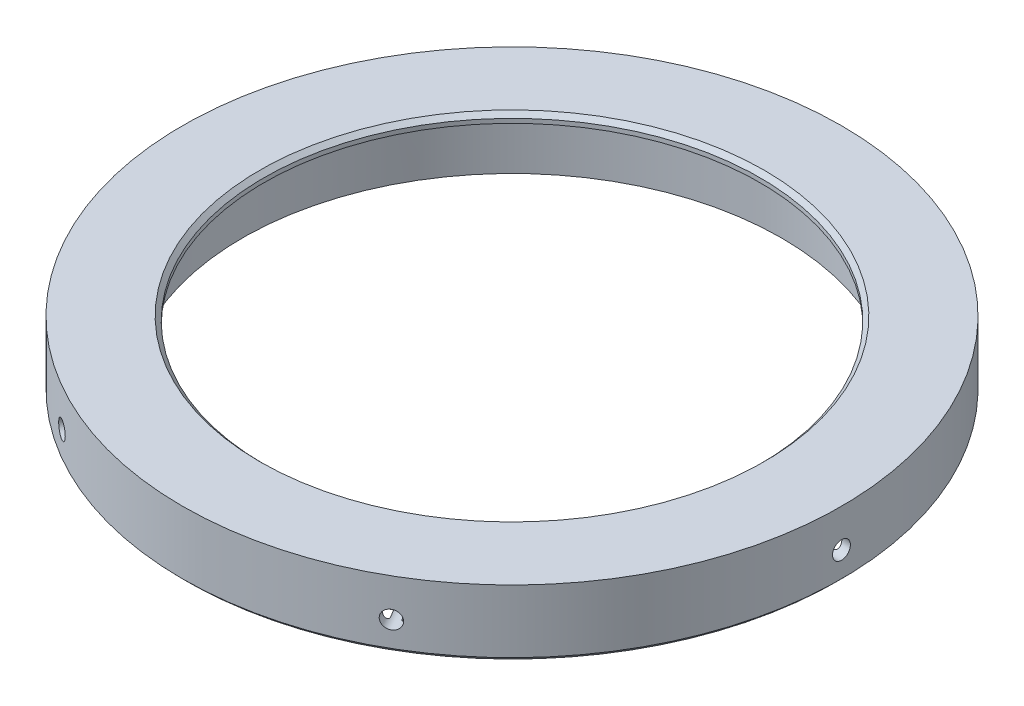
SolidWorks part; units mm, degrees
ref_plane "Front" through (0, 0, 0) normal (0, 0, 1) x (1, 0, 0)
ref_plane "Top" through (0, 0, 0) normal (0, 1, 0) x (1, 0, 0)
ref_plane "Right" through (0, 0, 0) normal (1, 0, 0) x (0, 0, -1)
sketch "Skizze1" plane through (0, 0, 0) normal (0, 1, 0) x (1, 0, 0)
  circle A0 centre (0, 0) radius 37.5 construction
  circle A1 centre (0, 0) radius 37.5 construction
  circle A2 centre (0, 0) radius 37.7
  circle A3 centre (0, 0) radius 47.5 construction
  circle A4 centre (0, 0) radius 47.5 construction
  circle A5 centre (0, 0) radius 46.1
  dimension "D1" = 0.2
  dimension "D2" = 1.4
extrude "Aufsatz-Linear austragen1" add sketch "Skizze1" along normal blind 1.2
sketch "Skizze2" plane through (0, 0, 0) normal (0, -1, 0) x (1, 0, 0)
  circle A0 centre (0, 0) radius 44.9
  circle A1 centre (0, 0) radius 46.1
  circle A2 centre (0, 0) radius 46.1
  circle A3 centre (0, 0) radius 37.7 construction
  circle A4 centre (0, 0) radius 37.7
  circle A5 centre (0, 0) radius 38.9
  circle M2 centre (0, 0) radius 46.1
  circle M3 centre (0, 0) radius 37.7
  dimension "D1" = 0
  dimension "D2" = 1.2
  dimension "D3" = 1.2
extrude "Aufsatz-Linear austragen2" add sketch "Skizze2" along normal up to surface (8.2 mm away) contours A5 M3 | A0 M2 region at (-45.9696, 0, 0) region at (-37.7997, 0, 0)
sketch "Skizze3" plane through (0, 1.2, 0) normal (0, 1, 0) x (1, 0, 0)
  circle A0 centre (0, 0) radius 37.7 construction
  circle A1 centre (0, 0) radius 37.7
  circle A2 centre (0, 0) radius 34.7
  arc A3 (-3.192, 34.5529) -> (-28.3277, 20.0408) centre (0, 0) ccw construction
extrude "Aufsatz-Linear austragen3" add sketch "Skizze3" against normal up to surface (1.2 mm away) up to face at (0, 0, -44.9)
sketch "Skizze5" plane through (0, 0, 0) normal (0, 1, 0) x (1, 0, 0)
  line L0 (0, 0) -> (0, 49.7873) construction
  line L1 (0.6, 38.8954) -> (0.6, 44.896)
  line L2 (-0.6, 38.8954) -> (-0.6, 44.896)
  line L3 (-0.6, 0) -> (-0.6, 49.7873) construction
  line L4 (0.6, 0) -> (0.6, 49.7873) construction
  line L5 (18.9281, 33.9844) -> (21.9284, 39.1811)
  line L6 (19.9673, 33.3844) -> (22.9676, 38.5811)
  line L7 (33.3844, 19.9673) -> (38.5811, 22.9676)
  line L8 (33.9844, 18.9281) -> (39.1811, 21.9284)
  line L9 (38.8954, 0.6) -> (44.896, 0.6)
  line L10 (38.8954, -0.6) -> (44.896, -0.6)
  line L11 (33.9844, -18.9281) -> (39.1811, -21.9284)
  line L12 (33.3844, -19.9673) -> (38.5811, -22.9676)
  line L13 (19.9673, -33.3844) -> (22.9676, -38.5811)
  line L14 (18.9281, -33.9844) -> (21.9284, -39.1811)
  line L15 (0.6, -38.8954) -> (0.6, -44.896)
  line L16 (-0.6, -38.8954) -> (-0.6, -44.896)
  line L17 (-18.9281, -33.9844) -> (-21.9284, -39.1811)
  line L18 (-19.9673, -33.3844) -> (-22.9676, -38.5811)
  line L19 (-33.3844, -19.9673) -> (-38.5811, -22.9676)
  line L20 (-33.9844, -18.9281) -> (-39.1811, -21.9284)
  line L21 (-38.8954, -0.6) -> (-44.896, -0.6)
  line L22 (-38.8954, 0.6) -> (-44.896, 0.6)
  line L23 (-33.9844, 18.9281) -> (-39.1811, 21.9284)
  line L24 (-33.3844, 19.9673) -> (-38.5811, 22.9676)
  line L25 (-19.9673, 33.3844) -> (-22.9676, 38.5811)
  line L26 (-18.9281, 33.9844) -> (-21.9284, 39.1811)
  circle A0 centre (0, 0) radius 38.9 construction
  circle A1 centre (0, 0) radius 44.9 construction
  arc A2 (0.6, 38.8954) -> (-0.6, 38.8954) centre (0, 0) ccw
  arc A3 (0.6, 44.896) -> (-0.6, 44.896) centre (0, 0) ccw
  arc A4 (22.9676, 38.5811) -> (21.9284, 39.1811) centre (0, 0) ccw
  arc A5 (19.9673, 33.3844) -> (18.9281, 33.9844) centre (0, 0) ccw
  arc A6 (39.1811, 21.9284) -> (38.5811, 22.9676) centre (0, 0) ccw
  arc A7 (33.9844, 18.9281) -> (33.3844, 19.9673) centre (0, 0) ccw
  arc A8 (44.896, -0.6) -> (44.896, 0.6) centre (0, 0) ccw
  arc A9 (38.8954, -0.6) -> (38.8954, 0.6) centre (0, 0) ccw
  arc A10 (38.5811, -22.9676) -> (39.1811, -21.9284) centre (0, 0) ccw
  arc A11 (33.3844, -19.9673) -> (33.9844, -18.9281) centre (0, 0) ccw
  arc A12 (21.9284, -39.1811) -> (22.9676, -38.5811) centre (0, 0) ccw
  arc A13 (18.9281, -33.9844) -> (19.9673, -33.3844) centre (0, 0) ccw
  arc A14 (-0.6, -44.896) -> (0.6, -44.896) centre (0, 0) ccw
  arc A15 (-0.6, -38.8954) -> (0.6, -38.8954) centre (0, 0) ccw
  arc A16 (-22.9676, -38.5811) -> (-21.9284, -39.1811) centre (0, 0) ccw
  arc A17 (-19.9673, -33.3844) -> (-18.9281, -33.9844) centre (0, 0) ccw
  arc A18 (-39.1811, -21.9284) -> (-38.5811, -22.9676) centre (0, 0) ccw
  arc A19 (-33.9844, -18.9281) -> (-33.3844, -19.9673) centre (0, 0) ccw
  arc A20 (-44.896, 0.6) -> (-44.896, -0.6) centre (0, 0) ccw
  arc A21 (-38.8954, 0.6) -> (-38.8954, -0.6) centre (0, 0) ccw
  arc A22 (-38.5811, 22.9676) -> (-39.1811, 21.9284) centre (0, 0) ccw
  arc A23 (-33.3844, 19.9673) -> (-33.9844, 18.9281) centre (0, 0) ccw
  arc A24 (-21.9284, 39.1811) -> (-22.9676, 38.5811) centre (0, 0) ccw
  arc A25 (-18.9281, 33.9844) -> (-19.9673, 33.3844) centre (0, 0) ccw
  point P59 (0, 0)
  dimension "D1" = 0.6
  dimension "D2" = 0.6
  dimension "D3" = 12
extrude "Aufsatz-Linear austragen5" add sketch "Skizze5" against normal up to surface (8.2 mm away) up to face at (0, -8.2, -44.9)
chamfer "Fase1" distance 0.6 angle 45 2 edges at (0, -8.2, -46.1) (0, 1.2, 34.7)
fillet "Verrundung1" radius 0.6 48 edges at (22.9676, -4.1, 38.5811) (19.9673, -4.1, 33.3844) (39.1811, -4.1, 21.9284) (38.5811, -4.1, 22.9676) (33.3844, -4.1, 19.9673) (33.9844, -4.1, 18.9281) (44.896, -4.1, 0.6) (38.8954, -4.1, 0.6) (38.8954, -4.1, -0.6) (44.896, -4.1, -0.6) (38.5811, -4.1, -22.9676) (39.1811, -4.1, -21.9284) (33.9844, -4.1, -18.9281) (33.3844, -4.1, -19.9673) (19.9673, -4.1, -33.3844) (22.9676, -4.1, -38.5811) (21.9284, -4.1, -39.1811) (18.9281, -4.1, -33.9844) (0.6, -4.1, -38.8954) (0.6, -4.1, -44.896) (-0.6, -4.1, -44.896) (-0.6, -4.1, -38.8954) (-18.9281, -4.1, -33.9844) (-21.9284, -4.1, -39.1811) (-22.9676, -4.1, -38.5811) (-19.9673, -4.1, -33.3844) (-33.3844, -4.1, -19.9673) (-38.5811, -4.1, -22.9676) (-39.1811, -4.1, -21.9284) (-33.9844, -4.1, -18.9281) (-38.8954, -4.1, -0.6) (-44.896, -4.1, -0.6) (-44.896, -4.1, 0.6) (-39.1811, -4.1, 21.9284) (-33.9844, -4.1, 18.9281) (-38.8954, -4.1, 0.6) (-33.3844, -4.1, 19.9673) (-19.9673, -4.1, 33.3844) (-22.9676, -4.1, 38.5811) (-38.5811, -4.1, 22.9676) (-21.9284, -4.1, 39.1811) (-18.9281, -4.1, 33.9844) (-0.6, -4.1, 38.8954) (-0.6, -4.1, 44.896) (0.6, -4.1, 44.896) (0.6, -4.1, 38.8954) (18.9281, -4.1, 33.9844) (21.9284, -4.1, 39.1811)
ref_axis "Achse1" through (0, -50, 0) along (0, 1, 0)
sketch "Skizze8" plane through (0, 0, 0) normal (1, 0, 0) x (0, 0, -1)
  circle A0 centre (0, -4.1) radius 1.25 construction
  circle A1 centre (0, -4.1) radius 1.25
extrude "Schnitt-Linear austragen2" cut sketch "Skizze8" against normal blind 9 from offset 50
pattern_circular "Kreismuster2" count 6 over 360 about axis through (0, -50, 0) along (0, 1, 0) of "Schnitt-Linear austragen2"
sketch "Skizze9" plane through (0, 0, 0) normal (0, 1, 0) x (1, 0, 0)
  line L0 (0, 0) -> (59.14, 0)
  line L1 (59.14, 0) -> (59.14, -54.8073)
  line L2 (59.14, -54.8073) -> (-31.643, -54.8073)
  line L3 (-31.643, -54.8073) -> (0, 0)
  dimension "D1" = 120
extrude "Schnitt-Linear austragen3" [suppressed] cut sketch "Skizze9" against normal through all both and the other way through all
